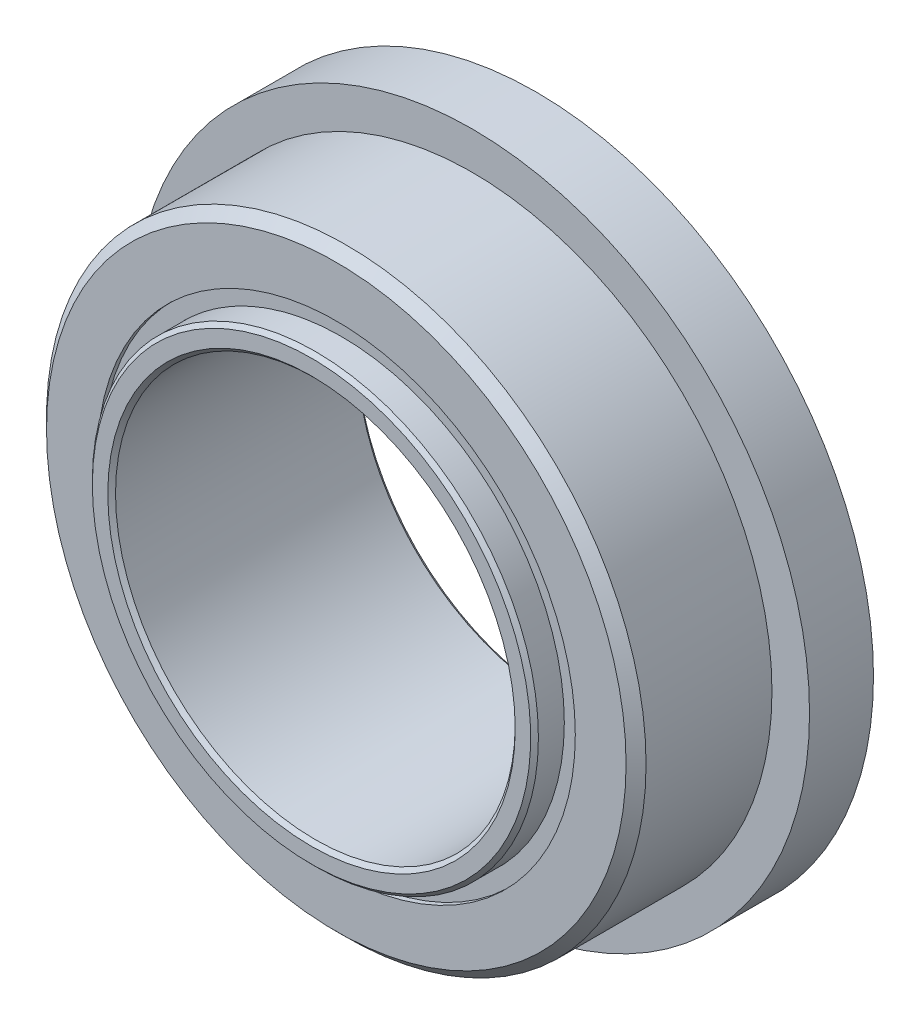
SolidWorks part; units mm, degrees
note: '?' marks a value the reader was unsure of.
ref_plane "Front Plane" through (0, 0, 0) normal (0, 0, 1) x (1, 0, 0)
ref_plane "Top Plane" through (0, 0, 0) normal (0, 1, 0) x (1, 0, 0)
ref_plane "Right Plane" through (0, 0, 0) normal (1, 0, 0) x (0, 0, -1)
sketch "Sketch1" plane through (0, 0, 0) normal (1, 0, 0) x (0, 0, -1)
  line L0 (-1.5875, 0) -> (1.5875, 0) construction
  line L1 (0, 4.7625) -> (0, -4.7625) construction
  line L2 (1.4287, 4.7625) -> (-1.4287, 4.7625)
  line L3 (-1.4287, 4.7625) -> (-1.5875, 4.6037)
  line L4 (-1.5875, 4.6037) -> (-1.5875, 3.7973)
  line L5 (-1.5875, 3.7973) -> (-0.5213, 3.7973)
  line L6 (1.5875, 3.7973) -> (0.5213, 3.7973)
  line L7 (1.5875, 4.6037) -> (1.5875, 3.7973)
  line L8 (1.4287, 4.7625) -> (1.5875, 4.6037)
  line L9 (0, 4.7625) -> (0, 3.9688) construction
  line L10 (0, 3.9688) -> (0, 3.175) construction
  line L11 (1.5875, 3.5433) -> (1.5875, -3.5433) construction
  line L12 (1.9812, 3.5433) -> (0.4012, 3.5433)
  line L13 (-1.9812, 3.5433) -> (-1.9812, 3.175)
  line L14 (-1.9812, 3.175) -> (1.9812, 3.175)
  line L15 (1.9812, 3.175) -> (1.9812, 3.5433)
  line L16 (-1.9812, 3.3592) -> (1.9812, 3.3592) construction
  line L17 (-0.4012, 3.5433) -> (-1.9812, 3.5433)
  circle A1 centre (0, 3.8883) radius 0.5292 construction
  arc A2 (-0.5213, 3.7973) -> (0.5213, 3.7973) centre (0, 3.8883) cw
  arc A3 (-0.4012, 3.5433) -> (0.4012, 3.5433) centre (0, 3.8883) ccw
  point P14 (0, 3.175)
  dimension "D4" = 1.0583
  dimension "Width" = 3.175
  dimension "OD" = 9.525
  dimension "D1" = 45
  dimension "D2" = 0.1588
  dimension "Inner Ring" = 7.0866
  dimension "Ring Width" = 3.9624
  dimension "D5" = 0.254
  dimension "D3" = 0.3683
revolve "Revolve1" add sketch "Sketch1" angle 360 about L0
sketch "Sketch4" plane through (0, 0, 0) normal (1, 0, 0) x (0, 0, -1)
  line L0 (-0.5292, 3.8883) -> (0.5292, 3.8883)
  circle A0 centre (0, 3.8883) radius 0.5292 construction
  arc A2 (-0.5292, 3.8883) -> (0.5292, 3.8883) centre (0, 3.8883) cw
revolve "Revolve4" add sketch "Sketch4" angle 360 about L0
chamfer "Chamfer1" distance 0.0614 angle 45 4 edges at (3.5433, 0, 1.9812) (3.175, 0, 1.9812) (3.175, 0, -1.9812) (3.5433, 0, -1.9812)
ref_axis "Axis1" through (0, 0, -1.5875) along (0, 0, 1)?
pattern_circular "CirPattern1" count 12 every 30 about axis through (0, 0, 0) along (0, 0, 1) of bodies 104
sketch "Sketch5" plane through (0, 0, 0) normal (1, 0, 0) x (0, 0, -1)
  line L0 (-1.5875, 3.7973) -> (-0.5213, 3.7973) construction
  line L1 (-1.5081, 3.7973) -> (-0.5292, 3.7973)
  line L2 (-1.5081, 3.7973) -> (-1.5081, 3.5433)
  line L3 (-1.5081, 3.5433) -> (-0.5292, 3.5433)
  line L4 (-0.5292, 3.7973) -> (-0.5292, 3.5433)
  line L6 (1.5875, 3.7973) -> (0.5213, 3.7973) construction
  line L7 (1.5081, 3.7973) -> (0.5292, 3.7973)
  line L8 (1.5081, 3.7973) -> (1.5081, 3.5433)
  line L9 (1.5081, 3.5433) -> (0.5292, 3.5433)
  line L10 (0.5292, 3.7973) -> (0.5292, 3.5433)
  line L12 (-1.4287, 4.7625) -> (-1.5875, 4.6037) construction
  line L13 (-0.4012, 3.5433) -> (-1.9812, 3.5433) construction
  line L14 (1.9812, 3.5433) -> (0.4012, 3.5433) construction
  point P18 (-1.5081, 4.6831)
revolve "Revolve5" add sketch "Sketch5" angle 360 about L0
sketch "Sketch6" plane through (0, 0, 0) normal (1, 0, 0) x (0, 0, -1)
  line L1 (1.5875, 3.7973) -> (0.5715, 3.7973)
  line L2 (1.5875, 3.7973) -> (1.5875, 5.3594)
  line L3 (1.5875, 5.3594) -> (0.5715, 5.3594)
  line L4 (0.5715, 3.7973) -> (0.5715, 5.3594)
  line L5 (1.5875, 0) -> (-1.5875, 0) construction
  dimension "Flange OD" = 10.7188
  dimension "Th" = 1.016
revolve "Revolve6" add sketch "Sketch6" angle 360 about L5
equation "\"D2@Sketch1\" = \"Width@Sketch1\"*.05"
equation "\"D2@CirPattern1\" = 360/\"Balls@CirPattern1\""
equation "\"D4@Sketch1\"=\"Width@Sketch1\"/3"
equation "\"D1@Chamfer1\"=\"D3@Sketch1\"/6"
